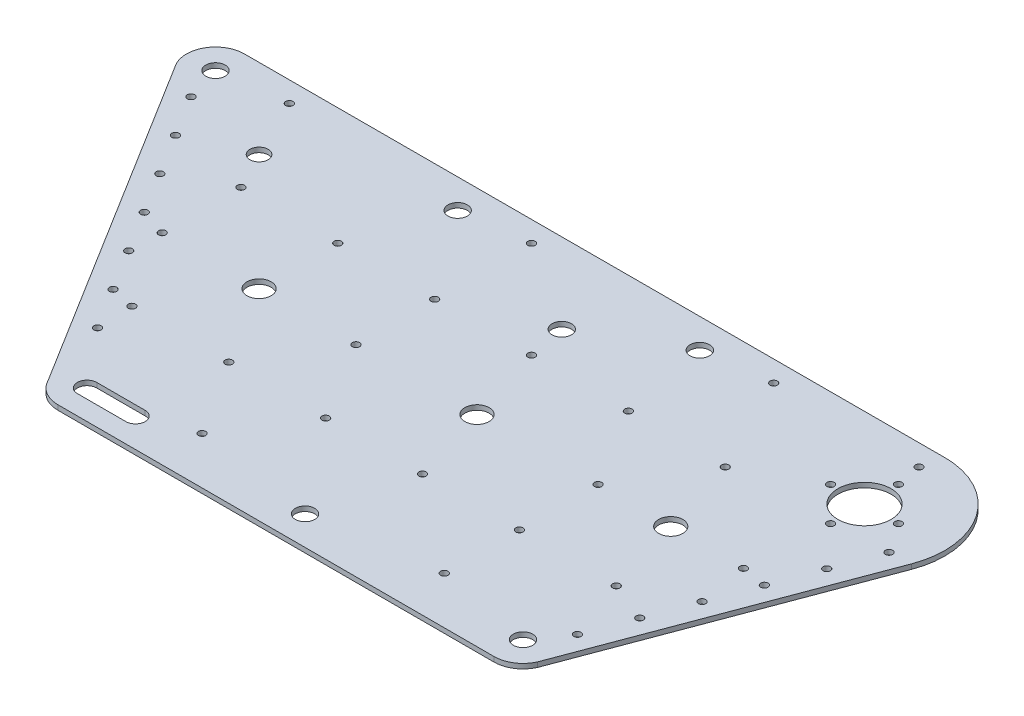
SolidWorks part; units mm, degrees
ref_plane "Front Plane" through (0, 0, 0) normal (0, 0, 1) x (1, 0, 0)
ref_plane "Top Plane" through (0, 0, 0) normal (0, 1, 0) x (1, 0, 0)
ref_plane "Right Plane" through (0, 0, 0) normal (1, 0, 0) x (0, 0, -1)
sketch "Sketch2" plane through (0, 0, 0) normal (0, 1, 0) x (1, 0, 0)
  line L0 (-106.005, 144.9436) -> (182.9628, 145.1972)
  line L1 (160.9924, -19) -> (-18.9986, -19)
  line L2 (171.9007, -12) -> (214.0696, 100.3323)
  line L3 (-18.9986, -3) -> (1.0004, -3)
  line L4 (1.0003, -11) -> (-18.9986, -11)
  line L5 (-29.6999, -12.4286) -> (-116.0853, 126.6112)
  circle A0 centre (182.992, 112) radius 11
  circle A1 centre (-18.9988, 64) radius 5
  circle A2 centre (70.9964, 64) radius 5
  circle A3 centre (150.9927, 64) radius 5
  circle A4 centre (-78.996, 136.5) radius 1.5
  circle A5 centre (20.9989, 136.5) radius 1.5
  circle A6 centre (120.9939, 136.5) radius 1.5
  circle A7 centre (180.9909, 136.5) radius 1.5
  circle A8 centre (170.3325, 6.1186) radius 1.5
  circle A9 centre (177.3307, 24.8545) radius 1.5
  circle A10 centre (184.3286, 43.5896) radius 1.5
  circle A11 centre (191.3265, 62.3248) radius 1.5
  circle A12 centre (198.3244, 81.0602) radius 1.5
  circle A13 centre (-38.3619, 16.6713) radius 1.5
  circle A14 centre (-48.9163, 33.6588) radius 1.5
  circle A15 centre (-59.4708, 50.6466) radius 1.5
  circle A16 centre (-70.0255, 67.6347) radius 1.5
  circle A17 centre (-80.5803, 84.623) radius 1.5
  circle A18 centre (70.9966, -7) radius 4
  ellipse E0 centre (-105.9945, 133) end of major axis (-105.9945, 137) minor radius 4
  ellipse E1 centre (160.9926, -7) end of major axis (160.9926, -3) minor radius 4
  ellipse E2 centre (-18.9986, -7) end of major axis (-18.9986, -11) minor radius 4 (-18.9986, -3) -> (-18.9986, -11) ccw
  ellipse E3 centre (182.992, 112) end of major axis (182.992, 123) minor radius 11
  ellipse E4 centre (-105.9945, 133) end of major axis (-105.9945, 144.9436) minor radius 11.943 (-106.005, 144.9436) -> (-116.0853, 126.6112) ccw
  ellipse E5 centre (182.992, 112) end of major axis (182.992, 145.1972) minor radius 33.1955 (214.0696, 100.3323) -> (182.9628, 145.1972) ccw
  ellipse E6 centre (1.0003, -7) end of major axis (1.0004, -3) minor radius 4 (1.0003, -11) -> (1.0004, -3) ccw
  ellipse E7 centre (182.9908, 126) end of major axis (182.9908, 127.5) minor radius 1.4999
  ellipse E8 centre (196.9901, 112) end of major axis (196.9901, 113.5) minor radius 1.4999
  ellipse E9 centre (168.9915, 112) end of major axis (168.9915, 113.5) minor radius 1.4999
  ellipse E10 centre (182.9908, 98) end of major axis (182.9908, 99.5) minor radius 1.4999
  ellipse E11 centre (-18.9986, -7) end of major axis (-18.9986, -19) minor radius 11.9993 (-29.6999, -12.4286) -> (-18.9986, -19) ccw
  ellipse E12 centre (160.9926, -7) end of major axis (160.9926, 5) minor radius 11.9994 (160.9924, -19) -> (171.9007, -12) ccw
  ellipse E13 centre (120.9939, 0.5) end of major axis (120.994, 2) minor radius 1.4999
  ellipse E14 centre (20.9989, 0.5) end of major axis (20.9989, 2) minor radius 1.4999
  ellipse E15 centre (120.9939, 64) end of major axis (120.994, 65.5) minor radius 1.4999
  ellipse E16 centre (20.9989, 64) end of major axis (20.9989, 65.5) minor radius 1.4999
  ellipse E17 centre (-58.997, 64) end of major axis (-58.997, 65.5) minor radius 1.4999
  ellipse E18 centre (180.9909, 64) end of major axis (180.9909, 65.5) minor radius 1.4999
  ellipse E22 centre (60.9969, 96.5) end of major axis (60.9969, 98) minor radius 1.4999
  ellipse E23 centre (140.9929, 96.5) end of major axis (140.9929, 98) minor radius 1.4999
  ellipse E24 centre (160.992, 31.5) end of major axis (160.992, 33) minor radius 1.4999
  ellipse E25 centre (80.996, 31.5) end of major axis (80.996, 33) minor radius 1.4999
  ellipse E26 centre (-18.9991, 96.5) end of major axis (-18.9991, 98) minor radius 1.4999
  ellipse E27 centre (-38.998, 31.5) end of major axis (-38.998, 33) minor radius 1.4999
  ellipse E31 centre (-101.6892, 118.5984) end of major axis (-101.6892, 120.0984) minor radius 1.4999
  ellipse E32 centre (-91.1347, 101.6106) end of major axis (-91.1347, 103.1106) minor radius 1.4999
  ellipse E38 centre (205.3225, 99.7958) end of major axis (205.3225, 101.2958) minor radius 1.4999
  ellipse E45 centre (20.9989, 96.5) end of major axis (20.9989, 98) minor radius 1.4999
  ellipse E46 centre (100.995, 96.5) end of major axis (100.995, 98) minor radius 1.4999
  ellipse E47 centre (-58.9971, 96.5) end of major axis (-58.997, 98) minor radius 1.4999
  ellipse E48 centre (0.9999, 31.5) end of major axis (1, 33) minor radius 1.4999
  ellipse E49 centre (40.9979, 31.5) end of major axis (40.9979, 33) minor radius 1.4999
  ellipse E50 centre (120.9939, 31.5) end of major axis (120.994, 33) minor radius 1.4999
  ellipse E51 centre (-66.9967, 112) end of major axis (-66.9966, 115.75) minor radius 3.7498
  ellipse E52 centre (57.9973, 112) end of major axis (53.9973, 112) minor radius 4
  ellipse E53 centre (-5.9995, 133) end of major axis (-5.9995, 137) minor radius 4
  ellipse E54 centre (93.9954, 133) end of major axis (93.9954, 137) minor radius 4
  dimension "D1" = 22
  dimension "D2" = 10
  dimension "D3" = 10
  dimension "D4" = 10
  dimension "D5" = 3
  dimension "D6" = 3
  dimension "D7" = 3
  dimension "D8" = 3
  dimension "D9" = 3
  dimension "D10" = 3
  dimension "D11" = 3
  dimension "D12" = 3
  dimension "D13" = 3
  dimension "D14" = 3
  dimension "D15" = 3
  dimension "D16" = 3
  dimension "D17" = 3
  dimension "D18" = 3
  dimension "D19" = 8
extrude "Boss-Extrude1" add sketch "Sketch2" along normal blind 2 contours L1 E12 L2 E5 L0 E4 L5 E11 E54 E53 E52 E51 E50 E49 E48 E47 E46 E45 E38 region at (58.7772, 0, -70.1515)
